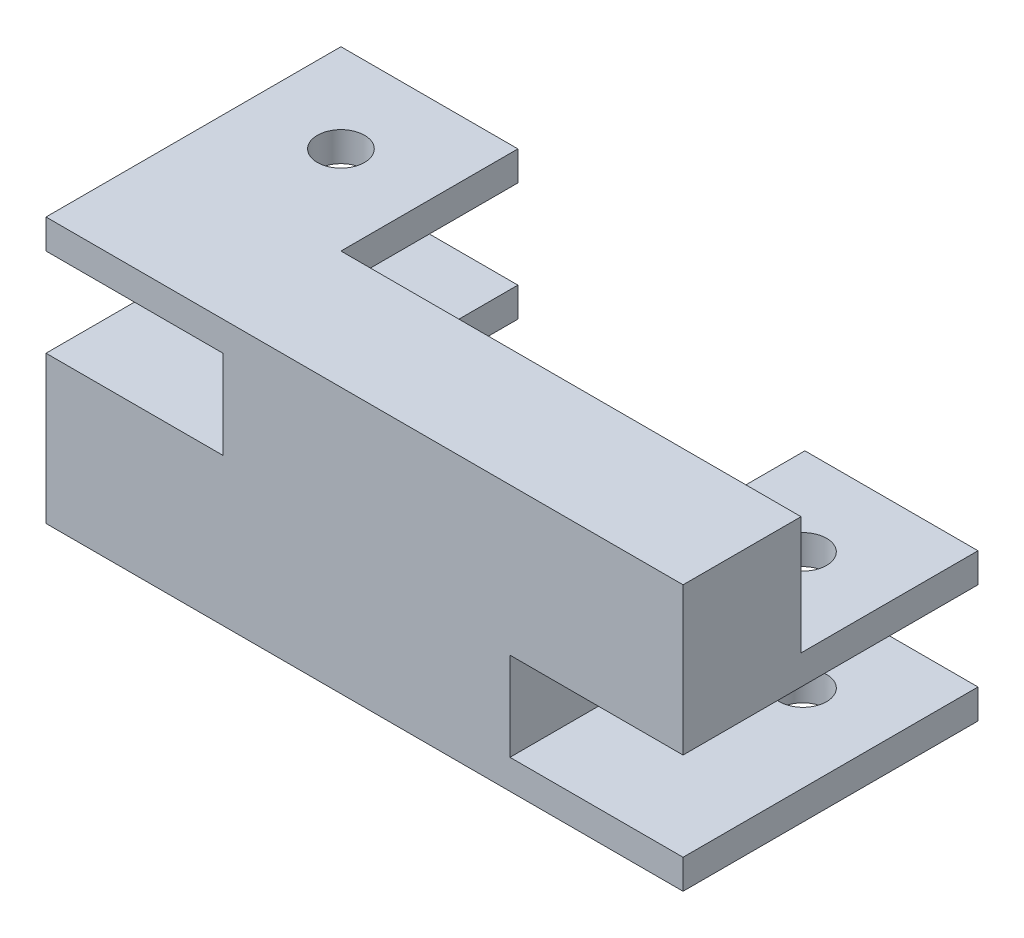
SolidWorks part; units mm, degrees
material "1060 Alloy"
ref_plane "Front Plane" through (0, 0, 0) normal (0, 0, 1) x (1, 0, 0)
ref_plane "Top Plane" through (0, 0, 0) normal (0, 1, 0) x (1, 0, 0)
ref_plane "Right Plane" through (0, 0, 0) normal (1, 0, 0) x (0, 0, -1)
sketch "Sketch1" plane through (0, 0, 0) normal (0, 0, 1) x (1, 0, 0)
  line L0 (-54, 22.5) -> (54, 22.5)
  line L5 (54, 22.5) -> (54, -2.5)
  line L6 (54, -2.5) -> (24.6547, -2.5)
  line L7 (24.6547, -2.5) -> (24.6547, -17.5)
  line L8 (24.6547, -17.5) -> (54, -17.5)
  line L9 (54, -17.5) -> (54, -22.5)
  line L10 (54, -22.5) -> (-54, -22.5)
  line L11 (-54, -22.5) -> (-54, 2.5)
  line L12 (-54, 2.5) -> (-24, 2.5)
  line L13 (-24, 2.5) -> (-24, 17.5)
  line L14 (-24, 17.5) -> (-54, 17.5)
  line L15 (-54, 17.5) -> (-54, 22.5)
  line L17 (-39, 17.5) -> (-39, 2.5) construction
  point P17 (0, 22.5)
  point P18 (0, -22.5)
  dimension "D5" = 15
  dimension "D1" = 30
  dimension "D2" = 39
  dimension "D6" = 15
  dimension "D3" = 5
  dimension "D4" = 2.5
  dimension "D7" = 5
  dimension "D8" = 5
extrude "Boss-Extrude1" add sketch "Sketch1" along normal blind 20
sketch "Sketch4" plane through (0, 0, 0) normal (0, 0, -1) x (-1, 0, 0)
  line L0 (-54, -2.5) -> (-54, 22.5) construction
  line L1 (-54, 2.5) -> (-24.6547, 2.5)
  line L2 (-54, 2.5) -> (-54, -2.5)
  line L3 (-54, -2.5) -> (-24.6547, -2.5)
  line L4 (-24.6547, 2.5) -> (-24.6547, -2.5)
  line L5 (-54, -17.5) -> (-24.6547, -17.5)
  line L6 (-54, -17.5) -> (-54, -22.5)
  line L7 (-54, -22.5) -> (-24.6547, -22.5)
  line L8 (-24.6547, -17.5) -> (-24.6547, -22.5)
  line L9 (-54, 22.5) -> (54, 22.5) construction
  line L10 (24, 2.5) -> (54, 2.5)
  line L11 (24, 2.5) -> (24, -2.5)
  line L12 (24, -2.5) -> (54, -2.5)
  line L13 (54, 2.5) -> (54, -2.5)
  line L14 (54, 17.5) -> (24, 17.5)
  line L15 (54, 17.5) -> (54, 22.5)
  line L16 (54, 22.5) -> (24, 22.5)
  line L17 (24, 17.5) -> (24, 22.5)
  line L19 (54, -22.5) -> (-54, -22.5) construction
  point P11 (54, 2.5)
  point P12 (-24.6547, 2.5)
  point P26 (-64.0544, 2.5)
  point P30 (-54, -2.5)
extrude "Boss-Extrude2" add sketch "Sketch4" along normal blind 30
sketch "Sketch2" plane through (0, 22.5, 0) normal (0, 1, 0) x (1, 0, 0)
  line L0 (-39, 15) -> (39.3273, 15) construction
  line L1 (-39, 15) -> (-39, 30) construction
  line L2 (24.6547, 30) -> (54, 30) construction
  line L3 (-54, 30) -> (-24, 30) construction
  line L4 (39.3273, 15) -> (39.3273, 30) construction
  circle A1 centre (39.3273, 15) radius 4
  circle A2 centre (-39, 15) radius 4
  dimension "D3" = 8
  dimension "D1" = 15
extrude "Actuator Shaft Passthrough" cut sketch "Sketch2" against normal offset from surface (50 mm away) 10 up to face at (36.3928, -17.5, -4) offset beyond the face yes
sketch "Sketch5" plane through (0, 22.5, 0) normal (0, 1, 0) x (1, 0, 0)
  circle A0 centre (-39, 15) radius 7.2 construction
  circle A1 centre (39.3273, 15) radius 7.2 construction
  dimension "D1" = 14.4
  dimension "D2" = 14.4
equation "\"D4@Sketch1\"=\"D3@Sketch1\"/2"
